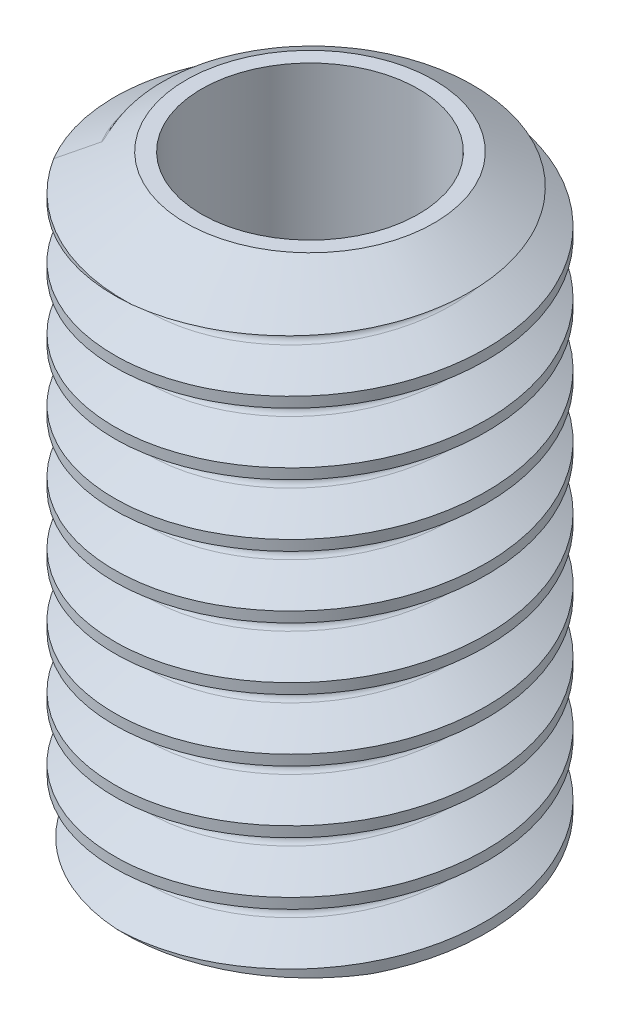
SolidWorks part; units mm, degrees
ref_plane "Front Plane" through (0, 0, 0) normal (0, 0, 1) x (1, 0, 0)
ref_plane "Top Plane" through (0, 0, 0) normal (0, 1, 0) x (1, 0, 0)
ref_plane "Right Plane" through (0, 0, 0) normal (1, 0, 0) x (0, 0, -1)
sketch "Sketch1" plane through (0, 0, 0) normal (0, 1, 0) x (1, 0, 0)
  circle A0 centre (0, 0) radius 3
  dimension "D1" = 6
extrude "Boss-Extrude1" add sketch "Sketch1" along normal blind 10
ref_plane "Plane1" through (0, 11, 0) normal (0, 1, 0) x (1, 0, 0)
sketch "Sketch3" plane through (0, 11, 0) normal (0, 1, 0) x (1, 0, 0)
  circle A0 centre (0, 0) radius 2.675
  dimension "D1" = 5.35
curve "Helix/Spiral1" pitch 1 height 12 radius 2.675 centre (0, 11, 0) axis (0, -1, 0) start towards (0, 0, 1)
sketch "Sketch4" plane through (0, 0, 0) normal (1, 0, 0) x (0, 0, -1)
  line L0 (0, 0) -> (0, 11) construction
  line L1 (0, 11) -> (-2.3865, 11) construction
  line L2 (0, 11) -> (0, 12) construction
  line L3 (0, 12) -> (-3, 12) construction
  line L4 (-3, 12) -> (-3, 10.5) construction
  line L5 (-2.3865, 11.0625) -> (-2.3865, 10.9375) construction
  line L6 (-2.3865, 11) -> (-3.3865, 11) construction
  line L7 (-2.3865, 11.0625) -> (-3.2525, 11.5625) construction
  line L8 (-2.3865, 10.9375) -> (-3.2525, 10.4375) construction
  line L9 (-2.4406, 11.0938) -> (-3, 11.4167)
  line L10 (-3, 11.4167) -> (-3, 10.5833)
  line L11 (-2.4406, 10.9062) -> (-3, 10.5833)
  arc A0 (-2.4406, 10.9062) -> (-2.4406, 11.0938) centre (-2.4948, 11) ccw
  point P9 (-3, 11.4167)
  point P18 (-3, 10.5833)
  dimension "D1" = 11
  dimension "D2" = 2.3865
  dimension "D3" = 1
  dimension "D4" = 3
  dimension "D5" = 1.5
  dimension "D6" = 0.0625
  dimension "D7" = 0.125
  dimension "D8" = 1
  dimension "D9" = 1
  dimension "D10" = 1
  dimension "D11" = 30
  dimension "D12" = 60
sweep "Cut-Sweep1" cut profiles "Sketch4" path "Helix/Spiral1" align with end faces yes
sketch "Sketch5" plane through (0, 0, 0) normal (0, 1, 0) x (1, 0, 0)
  circle A0 centre (0, 0) radius 1.75
  dimension "D1" = 3.5
extrude "Cut-Extrude3" cut sketch "Sketch5" along normal through all
sketch "Sketch6" plane through (0, 0, 0) normal (1, 0, 0) x (0, 0, -1)
  line L0 (3, 0) -> (0, 0) construction
  line L1 (0, 0) -> (0, 10) construction
  line L2 (2.6029, 10) -> (-2.0345, 10) construction
  line L3 (0, 10) -> (3, 10) construction
  line L4 (3, 10) -> (2, 10)
  line L5 (2, 10) -> (3, 9.4226)
  line L6 (3, 9.4226) -> (3, 10)
  line L7 (3, 0) -> (2, 0)
  line L8 (2, 0) -> (3, 0.5774)
  line L9 (3, 0.5774) -> (3, 0)
  dimension "D1" = 3
  dimension "D2" = 3
  dimension "D3" = 1
  dimension "D4" = 30
  dimension "D5" = 1
  dimension "D6" = 30
revolve "Cut-Revolve1" cut sketch "Sketch6" angle 360 about L1
